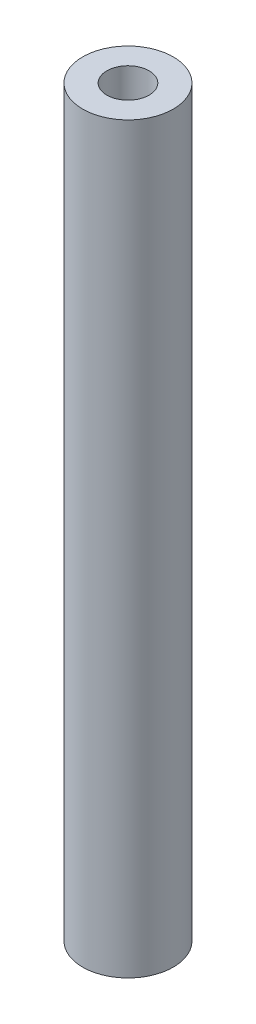
SolidWorks part; units mm, degrees
ref_plane "Front" through (0, 0, 0) normal (0, 0, 1) x (1, 0, 0)
ref_plane "Top" through (0, 0, 0) normal (0, 1, 0) x (1, 0, 0)
ref_plane "Right" through (0, 0, 0) normal (1, 0, 0) x (0, 0, -1)
sketch "Sketch1" plane through (0, 0, 0) normal (0, 1, 0) x (1, 0, 0)
  circle A0 centre (0, 0) radius 3
  circle A1 centre (0, 0) radius 1.4
  dimension "D1" = 2.8
  dimension "D2" = 6
extrude "Boss-Extrude1" add sketch "Sketch1" along normal blind 49.24
